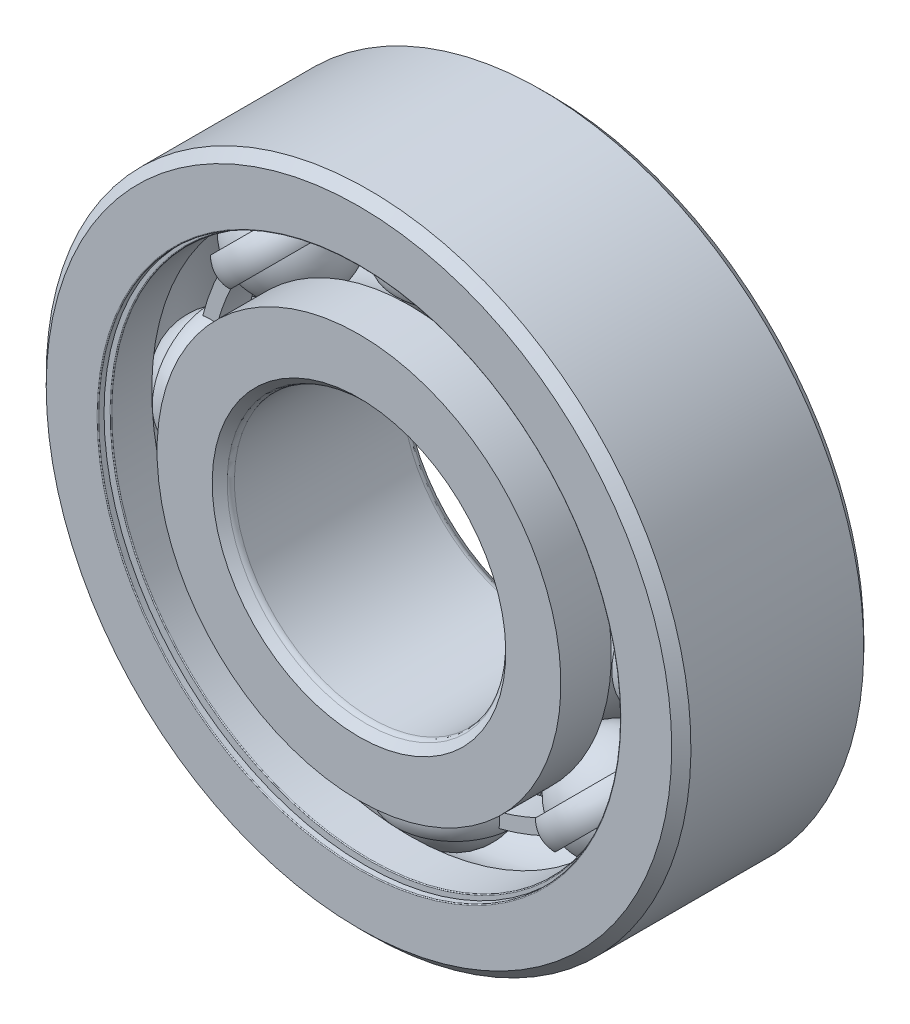
SolidWorks part; units mm, degrees
ref_plane "Front Plane" through (0, 0, 0) normal (0, 0, 1) x (1, 0, 0)
ref_plane "Top Plane" through (0, 0, 0) normal (0, 1, 0) x (1, 0, 0)
ref_plane "Right Plane" through (0, 0, 0) normal (1, 0, 0) x (0, 0, -1)
sketch "Sketch1" plane through (0, 0, 0) normal (0, 0, 1) x (1, 0, 0)
  line L0 (-23.5, 0) -> (23.5, 0) construction
  line L1 (-10, 0) -> (10, 0) construction
  circle A0 centre (0, 0) radius 10 construction
  circle A1 centre (0, 0) radius 23.5 construction
  point P3 (0, 0)
  point P6 (0, 0)
  point P7 (0, -10)
  point P11 (0, -23.5)
  point P12 (0, 10)
  point P13 (0, 23.5)
  dimension "OD" = 47
  dimension "ID" = 20
sketch "Sketch2" plane through (0, 0, 0) normal (1, 0, 0) x (0, 0, -1)
  line L0 (-7, 23.5) -> (7, 23.5) construction
  line L1 (0, 23.5) -> (0, -23.5) construction
  line L2 (6.3, 23.5) -> (-6.3, 23.5)
  line L3 (-6.3, 23.5) -> (-7, 22.8)
  line L4 (-7, 22.8) -> (-7, 18.7808)
  line L5 (-7, 18.7808) -> (-3.325, 18.7808)
  line L6 (7, 18.7808) -> (3.325, 18.7808)
  line L7 (7, 22.8) -> (7, 18.7808)
  line L8 (6.3, 23.5) -> (7, 22.8)
  line L9 (0, 23.5) -> (0, 16.75) construction
  line L10 (0, 16.75) -> (0, 10) construction
  line L11 (0, 23.5) -> (0, -23.5) construction
  line L12 (-7, 0) -> (7, 0) construction
  line L13 (7, 10) -> (-7, 10) construction
  line L14 (0, 20.6461) -> (0, 12.8539) construction
  line L15 (-7, -10) -> (7, -10) construction
  line L16 (-7, -10) -> (-7, 10) construction
  line L17 (7, 23.5) -> (7, -23.5) construction
  arc A0 (-3.325, 18.7808) -> (3.325, 18.7808) centre (0, 16.75) cw
  circle A1 centre (0, 16.75) radius 3.8961 construction
  point P14 (0, 10)
  point P17 (0, 0)
  point P21 (0, 23.5)
  point P29 (0, 10)
  point P30 (0, -10)
  point P35 (0, 20.6461)
  dimension "Approx. Ball Dia." = 7.7922
  dimension "Width" = 14
  dimension "D1" = 45
  dimension "D2" = 0.7
  dimension "D3" = 6.65
  dimension "D4" = 2.0308
  dimension "For Shaft Diameter" = 20
  dimension "For Housing ID" = 47
sketch "Sketch3" plane through (0, 0, 0) normal (1, 0, 0) x (0, 0, -1)
  line L0 (6.3, 23.5) -> (7, 22.8) construction
  line L1 (7, 22.8) -> (7, 18.7808) construction
  line L2 (7, 18.7808) -> (3.325, 18.7808) construction
  line L3 (-7, 18.7808) -> (-3.325, 18.7808) construction
  line L4 (-7, 22.8) -> (-7, 18.7808) construction
  line L5 (-6.3, 23.5) -> (-7, 22.8) construction
  line L6 (6.3, 23.5) -> (-6.3, 23.5) construction
  line L7 (6.3, 23.5) -> (7, 22.8)
  line L8 (7, 22.8) -> (7, 18.7808)
  line L9 (7, 18.7808) -> (3.325, 18.7808)
  line L10 (-7, 18.7808) -> (-3.325, 18.7808)
  line L11 (-7, 22.8) -> (-7, 18.7808)
  line L12 (-6.3, 23.5) -> (-7, 22.8)
  line L13 (6.3, 23.5) -> (-6.3, 23.5)
  arc A0 (3.325, 18.7808) -> (-3.325, 18.7808) centre (0, 16.75) ccw construction
  arc A1 (3.325, 18.7808) -> (-3.325, 18.7808) centre (0, 16.75) ccw
revolve "Revolve1" add sketch "Sketch3" angle 360 about L12
sketch "Sketch8" plane through (0, 0, 0) normal (1, 0, 0) x (0, 0, -1)
  line L0 (-7, 18.7808) -> (-3.325, 18.7808) construction
  line L1 (-6.552, 18.7808) -> (-6.3, 18.7808)
  line L2 (-6.552, 18.7808) -> (-6.552, 20.3538) construction
  line L3 (-6.552, 20.3538) -> (-6.3, 20.3538)
  line L4 (-6.3, 18.7808) -> (-6.3, 20.3538)
  line L5 (7, 18.7808) -> (3.325, 18.7808) construction
  line L6 (6.3, 18.7808) -> (6.552, 18.7808)
  line L7 (6.3, 18.7808) -> (6.3, 20.3538)
  line L8 (6.3, 20.3538) -> (6.552, 20.3538)
  line L9 (6.552, 18.7808) -> (6.552, 20.3538) construction
  line L10 (-6.3, 20.3538) -> (6.3, 20.3538) construction
  line L11 (0, 23.5) -> (0, -23.5) construction
  line L12 (-6.552, 20.3538) -> (-6.552, 21.9269) construction
  line L13 (-6.552, 21.9269) -> (-6.552, 23.5) construction
  line L14 (-7, 23.5) -> (7, 23.5) construction
  line L15 (-6.552, 18.7808) -> (-7, 18.7808)
  line L16 (-7, 18.7808) -> (-7, 19.0328)
  line L17 (-7, 22.8) -> (-7, 18.7808) construction
  line L18 (-7, 19.0328) -> (-6.552, 19.0328)
  line L19 (-6.552, 19.0328) -> (-6.552, 20.3538)
  line L20 (6.552, 18.7808) -> (7, 18.7808)
  line L21 (7, 18.7808) -> (7, 19.0328)
  line L22 (7, 22.8) -> (7, 18.7808) construction
  line L23 (7, 19.0328) -> (6.552, 19.0328)
  line L24 (6.552, 19.0328) -> (6.552, 20.3538)
  point P12 (0, 20.3538)
  dimension "D1" = 12.6
  dimension "D2" = 0.252
revolve "Cut-Revolve1" cut sketch "Sketch8" angle 360 about L12
sketch "Sketch4" plane through (0, 0, 0) normal (1, 0, 0) x (0, 0, -1)
  line L0 (0, 23.5) -> (0, -23.5) construction
  line L1 (0, 23.5) -> (0, -23.5) construction
  line L2 (-6.3, 10) -> (-7, 10.7)
  line L3 (-7, 10.7) -> (-7, 14.7192)
  line L5 (-7, 14.7192) -> (-3.325, 14.7192)
  line L6 (-6.3, 10) -> (6.3, 10)
  line L8 (6.3, 10) -> (7, 10.7)
  line L10 (7, 10.7) -> (7, 14.7192)
  line L11 (7, 14.7192) -> (3.325, 14.7192)
  line L12 (-7, 22.8) -> (-7, 18.7808) construction
  line L13 (6.3, 23.5) -> (7, 22.8) construction
  line L15 (7, -22.8) -> (7, 22.8) construction
  line L16 (6.3, 23.5) -> (6.3, -23.5) construction
  arc A1 (3.325, 14.7192) -> (-3.325, 14.7192) centre (0, 16.75) cw
  circle A2 centre (0, 16.75) radius 3.8961 construction
  point P1 (0, 10)
revolve "Revolve2" add sketch "Sketch4" angle 360 about L12
sketch "Sketch5" plane through (0, 0, 0) normal (1, 0, 0) x (0, 0, -1)
  line L0 (-3.8961, 16.75) -> (3.8961, 16.75)
  arc A2 (-3.8961, 16.75) -> (3.8961, 16.75) centre (0, 16.75) cw
  arc A3 (3.325, 18.7808) -> (-3.325, 18.7808) centre (0, 16.75) ccw construction
revolve "Revolve3" add sketch "Sketch5" angle 360 about L0
sketch "Sketch6" plane through (0, 0, 0) normal (1, 0, 0) x (0, 0, -1)
  line L0 (-3.325, 18.7808) -> (-3.325, 17.7654) construction
  line L1 (-3.325, 17.7654) -> (-3.325, 16.75) construction
  line L2 (-3.325, 16.75) -> (-3.325, 15.7346) construction
  line L3 (-3.325, 15.7346) -> (-3.325, 14.7192) construction
  line L4 (-7, 17.7654) -> (-6.4602, 17.7654) construction
  line L5 (-3.325, 17.7654) -> (-3.325, 15.7346) construction
  line L7 (-6.4602, 17.7654) -> (-5.9205, 17.7654) construction
  line L8 (-5.9205, 17.7654) -> (-5.3807, 17.7654) construction
  line L10 (0, 23.5) -> (0, -23.5) construction
  line L11 (0, 23.5) -> (0, -23.5) construction
  line L12 (-7, 18.7808) -> (-7, 17.7654) construction
  line L13 (-4.3012, 17.7654) -> (-3.7615, 17.7654) construction
  line L14 (-7, 22.8) -> (-7, -22.8) construction
  line L15 (-7, 17.7654) -> (-7, 16.75) construction
  line L16 (-7, 16.75) -> (-7, 15.7346) construction
  line L17 (-7, 15.7346) -> (-7, 14.7192) construction
  line L18 (-5.3807, 17.7654) -> (-4.841, 17.7654) construction
  line L19 (-4.841, 17.7654) -> (-4.3012, 17.7654) construction
  line L20 (-3.7615, 17.7654) -> (-4.3012, 17.7654)
  line L21 (-7, 15.7346) -> (-6.4602, 15.7346) construction
  line L22 (-6.4602, 15.7346) -> (-5.9205, 15.7346) construction
  line L23 (-5.9205, 15.7346) -> (-5.3807, 15.7346) construction
  line L24 (-5.3807, 15.7346) -> (-4.841, 15.7346) construction
  line L25 (-4.841, 15.7346) -> (-4.3012, 15.7346) construction
  line L26 (-4.3012, 15.7346) -> (-3.7615, 15.7346) construction
  line L27 (-3.7615, 15.7346) -> (-4.3012, 15.7346)
  line L28 (-4.841, 17.7654) -> (-4.841, 15.7346) construction
  line L30 (-4.5711, 17.7654) -> (-4.5711, 15.7346) construction
  circle A0 centre (0, 16.75) radius 3.8961 construction
  arc A2 (-4.3012, 15.7346) -> (-4.3012, 17.7654) centre (-2.526, 16.75) cw
  arc A3 (-3.7615, 17.7654) -> (-3.7615, 15.7346) centre (0, 16.75) ccw
revolve "Revolve4" add sketch "Sketch6" angle 360 about L11
sketch "Sketch7" plane through (0, 0, 0) normal (0, 0, 1) x (1, 0, 0)
  line L0 (-3.8961, 16.75) -> (3.8961, 16.75) construction
  line L1 (0, 12.8539) -> (0, 20.6461) construction
  line L2 (0, 0) -> (6.7455, 15.3317) construction
  line L8 (0, 23.5) -> (0, -23.5) construction
  line L9 (12.3486, 11.317) -> (13.0971, 12.0031)
  line L10 (0, 23.5) -> (0, -23.5) construction
  line L11 (0, 17.7654) -> (0, 16.75)
  arc A1 (12.3486, 11.317) -> (0, 16.75) centre (0, 0) ccw
  arc A2 (13.0971, 12.0031) -> (0, 17.7654) centre (0, 0) ccw
  dimension "D1" = 47.496
  dimension "D2" = 7.7922
extrude "Boss-Extrude1" add sketch "Sketch7" along normal mid plane 2.3333
pattern_circular "CirPattern1" count 8 over 360 about axis through (0, 0, 7) along (0, 0, -1) of bodies 104 134
pattern_circular "CirPattern2" count 8 over 360 about axis through (0, 0, 7) along (0, 0, -1) of "Revolve4", "Boss-Extrude1" reverse direction yes
fillet "Fillet1" radius 0.063 4 edges at (0, -18.7808, -6.3) (0, -19.0328, -7) (0, -18.7808, 6.3) (0, -19.0328, 7)
fillet "Fillet2" radius 0.525 2 edges at (0, -10, -6.3) (0, -10, 6.3)
ref_plane "Plane1" through (6.7455, 15.3317, 0) normal (0.4027, 0.9153, 0) x (0.9153, -0.4027, 0)
sketch "Sketch9" plane through (6.7455, 15.3317, 0) normal (0.4027, 0.9153, 0) x (0.9153, -0.4027, 0)
  line L0 (-3.1792, -1.1667) -> (-3.1792, -3.5)
  line L1 (-3.1792, -3.5) -> (-1.379, -3.5)
  line L2 (-1.379, -3.5) -> (0, -2.3429)
  line L3 (0, -2.3429) -> (1.379, -3.5)
  line L4 (1.379, -3.5) -> (3.1792, -3.5)
  line L5 (3.1792, -3.5) -> (3.1792, -1.1667)
  line L6 (3.1792, -1.1667) -> (-3.1792, -1.1667)
  line L7 (0, -1.1667) -> (0, 0) construction
  line L8 (-3.1792, -1.1667) -> (-3.1792, 0) construction
  dimension "D1" = 2.3333
  dimension "D2" = 1.1667
  dimension "D3" = 40
extrude "Boss-Extrude2" [suppressed] add sketch "Sketch9" along normal blind 3.4091 draft 15 and the other way blind 3.4091 draft 10 separate body draft outward yes other way draft outward yes
fillet "Fillet3" [suppressed] radius 0.7
mirror "Mirror1" [suppressed] about plane through (0, 0, 0) normal (0, 0, 1) of bodies 149
pattern_circular "CirPattern3" [suppressed] count 8 over 360 about axis through (0, 0, 7) along (0, 0, -1) of bodies 158 149
equation "\"D2@Sketch2\" = \"Width@Sketch2\" * .05"
equation "\"D3@Sketch2\"=\"Width@Sketch2\" * .475"
equation "\"D4@Sketch2\" =  (  (  ( \"OD@Sketch1\" - \"Width@Sketch2\" )  / 2 )  / 3.25 )  / 2.5"
equation "\"D1@Boss-Extrude1\" = \"Width@Sketch2\" / 6"
equation "\"D1@Sketch8\"=\"Width@Sketch2\"*.9"
equation "\"D2@Sketch8\"=\"D1@Sketch8\"*.02"
equation "\"D1@Fillet1\" = \"D2@Sketch8\" * .25"
equation "\"D1@Fillet2\" = \"D2@Sketch2\" * .75"
equation "\"Approx No of Balls\"= ( pi * \"OD@Sketch1\" ) * .4 / \"Approx. Ball Dia.@Sketch2\""
equation "\"D1@CirPattern1\"=\"Approx No of Balls\""
equation "\"D1@Sketch7\"=360/\"Approx No of Balls\""
equation "\"D1@CirPattern2\"=\"Approx No of Balls\""
equation "\"D2@Sketch7\"=\"Approx. Ball Dia.@Sketch2\""
equation "\"D2@Sketch9\"=\"d1@boss-extrude1\"*.5"
equation "\"D1@Sketch9\"=\"D2@Sketch9\"*2"
equation "\"D1@Boss-Extrude2\"=\"Approx. Ball Dia.@Sketch2\"*.4375"
equation "\"D2@Boss-Extrude2\"=\"D1@Boss-Extrude2\""
equation "\"D1@CirPattern3\"=\"Approx No of Balls\""
equation "\"D1@Fillet3\"=\"D1@Sketch9\" * .3"
